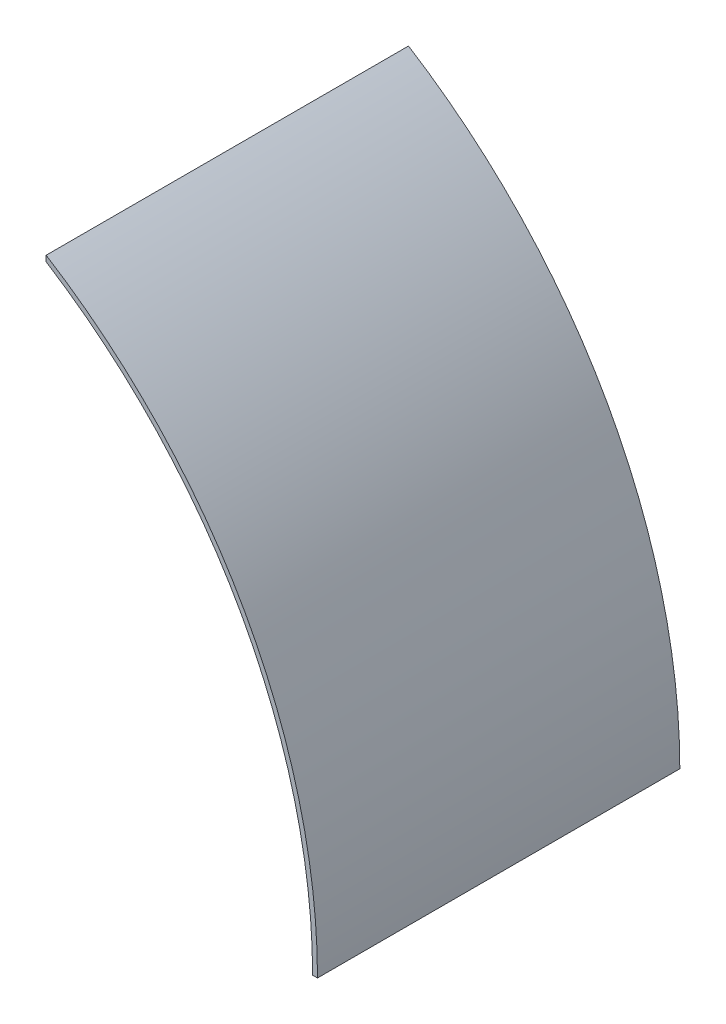
SolidWorks part; units mm, degrees
material "Plain Carbon Steel"
ref_plane "Front Plane" through (0, 0, 0) normal (0, 0, 1) x (1, 0, 0)
ref_plane "Top Plane" through (0, 0, 0) normal (0, 1, 0) x (1, 0, 0)
ref_plane "Right Plane" through (0, 0, 0) normal (1, 0, 0) x (0, 0, -1)
sketch "Sketch2" plane through (0, 0, 0) normal (0, 0, 1) x (1, 0, 0)
  line L0 (-177.8, 0) -> (177.8, 0) construction
  line L1 (0, 177.8) -> (0, -179.3189) construction
  line L2 (95.25, 0) -> (95.25, 108.9269) construction
  line L7 (95.25, 151.93) -> (95.25, 150.1342)
  line L8 (0, -179.3189) -> (0, -160.382) construction
  line L21 (177.8, 0) -> (179.3189, 0)
  circle A0 centre (0, 0) radius 177.8 construction
  circle A1 centre (0, 0) radius 179.3189 construction
  arc A2 (95.25, 150.1342) -> (177.8, 0) centre (0, 0) cw
  arc A3 (179.3189, 0) -> (95.25, 151.93) centre (0, 0) ccw
  dimension "D1" = 355.6
  dimension "D2" = 358.6378
  dimension "D3" = 95.25
extrude "Inner Ring - Right Side" add sketch "Sketch2" along normal blind 112.268
